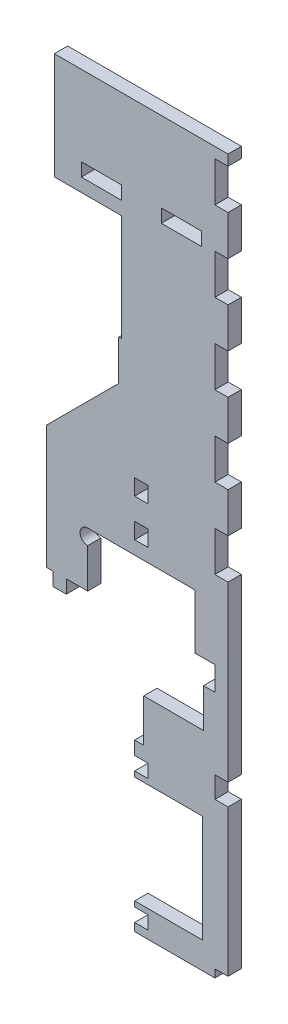
SolidWorks part; units mm, degrees
material "Balsa"
ref_plane "Plan de face" through (0, 0, 0) normal (0, 0, 1) x (1, 0, 0)
ref_plane "Plan de dessus" through (0, 0, 0) normal (0, 1, 0) x (1, 0, 0)
ref_plane "Plan de droite" through (0, 0, 0) normal (1, 0, 0) x (0, 0, -1)
sketch "Esquisse1" plane through (0, 0, 0) normal (0, 0, 1) x (1, 0, 0)
  line L0 (65.1211, 0) -> (30.1224, 0)
  line L2 (65.1211, 0) -> (65.1211, 270)
  line L3 (65.1211, 270) -> (0, 270)
  line L4 (0, 270) -> (0, 230)
  line L5 (0, 230) -> (24.1211, 230)
  line L6 (-2.8789, 101.7504) -> (12.493, 101.7504)
  line L7 (12.493, 101.7504) -> (12.493, 122.247)
  line L8 (12.493, 122.247) -> (52.693, 122.247)
  line L9 (52.693, 122.247) -> (52.693, 101.7504)
  line L10 (52.693, 101.7504) -> (55.9116, 101.7504)
  line L11 (1.3186, 101.7504) -> (30.1224, 101.7504) construction
  line L12 (55.9116, 101.7504) -> (55.9116, 78.2407)
  line L13 (55.9116, 78.2407) -> (33.5123, 78.2407)
  line L14 (33.5123, 78.2407) -> (33.5123, 62.2)
  line L15 (33.5123, 62.2) -> (30.1224, 62.2)
  line L16 (30.1224, 62.2) -> (30.1224, 57.2)
  line L17 (30.1224, 50.2) -> (55.6176, 50.2)
  line L18 (30.1224, 57.2) -> (35.1224, 57.2)
  line L19 (24.1211, 230) -> (24.1211, 175)
  line L20 (35.1224, 57.2) -> (35.1224, 52.2)
  line L21 (24.1211, 175) -> (-2.8789, 148)
  line L22 (-2.8789, 148) -> (-2.8789, 101.7504)
  line L23 (35.1224, 52.2) -> (30.1224, 52.2)
  line L24 (30.1224, 52.2) -> (30.1224, 50.2)
  line L25 (30.1224, 0) -> (30.1224, 3)
  line L26 (30.1224, 3) -> (35.1224, 3)
  line L27 (35.1224, 3) -> (35.1224, 8)
  line L30 (35.1224, 8) -> (30.1224, 8)
  line L31 (30.1224, 8) -> (30.1224, 10)
  line L32 (30.1224, 10) -> (55.6176, 10)
  line L33 (55.6176, 10) -> (55.6176, 50.2)
  dimension "D1" = 270
  dimension "D2" = 65.1211
  dimension "D3" = 40.2
  dimension "D4" = 2
  dimension "D5" = 20.4965
  dimension "D6" = 40.2
  dimension "D7" = 55
  dimension "D8" = 40
  dimension "D9" = 12.4281
  dimension "D10" = 25.4952
  dimension "D11" = 5
  dimension "D12" = 5
  dimension "D13" = 5
  dimension "D14" = 2
  dimension "D15" = 5
  dimension "D16" = 5
  dimension "D17" = 25.4952
  dimension "D18" = 135
  dimension "D19" = 41
  dimension "D20" = 68
extrude "Boss.-Extru.1" add sketch "Esquisse1" against normal blind 5
sketch "Esquisse2" plane through (0, 0, 0) normal (0, 0, 1) x (1, 0, 0)
  line L0 (52.693, 101.7504) -> (55.9116, 101.7504) construction
  line L1 (35.1224, 147.4016) -> (30.1224, 147.4016)
  line L2 (12.493, 122.247) -> (52.693, 122.247) construction
  line L3 (12.493, 101.7504) -> (12.493, 122.247) construction
  line L4 (35.1224, 147.4016) -> (35.1224, 141.4016)
  line L5 (35.1224, 141.4016) -> (30.1224, 141.4016)
  line L6 (30.1224, 147.4016) -> (30.1224, 141.4016)
  line L7 (35.1224, 133.247) -> (30.1224, 133.247)
  line L8 (35.1224, 133.247) -> (35.1224, 127.247)
  line L9 (35.1224, 127.247) -> (30.1224, 127.247)
  line L10 (30.1224, 133.247) -> (30.1224, 127.247)
  line L11 (55.9116, 101.7504) -> (60.186, 101.7504)
  line L12 (55.9116, 101.7504) -> (55.9116, 92.7704)
  line L13 (55.9116, 92.7704) -> (60.186, 92.7704)
  line L14 (60.186, 101.7504) -> (60.186, 92.7704)
  line L15 (52.693, 122.247) -> (52.693, 101.7504) construction
  line L16 (65.1211, 0) -> (65.1211, 270) construction
  line L17 (65.1211, 0) -> (60.2011, 0)
  line L18 (65.1211, 0) -> (65.1211, 3)
  line L19 (65.1211, 3) -> (60.2011, 3)
  line L20 (60.2011, 0) -> (60.2011, 3)
  line L21 (30.1224, 0) -> (65.1211, 0) construction
  line L22 (65.1211, 0) -> (65.1211, 270) construction
  line L23 (65.1211, 58) -> (60.2011, 58)
  line L24 (65.1211, 58) -> (65.1211, 66)
  line L25 (65.1211, 66) -> (60.2011, 66)
  line L26 (60.2011, 58) -> (60.2011, 66)
  line L27 (30.1224, 0) -> (65.1211, 0) construction
  line L28 (65.1211, 161) -> (60.2011, 161)
  line L29 (65.1211, 131) -> (60.2011, 131)
  line L30 (65.1211, 131) -> (65.1211, 146)
  line L31 (65.1211, 146) -> (60.2011, 146)
  line L32 (60.2011, 131) -> (60.2011, 146)
  line L33 (65.1211, 161) -> (65.1211, 176)
  line L34 (65.1211, 176) -> (60.2011, 176)
  line L35 (60.2011, 161) -> (60.2011, 176)
  line L36 (65.1211, 191) -> (60.2011, 191)
  line L37 (65.1211, 191) -> (65.1211, 206)
  line L38 (65.1211, 206) -> (60.2011, 206)
  line L39 (60.2011, 191) -> (60.2011, 206)
  line L40 (65.1211, 221) -> (60.2011, 221)
  line L41 (65.1211, 221) -> (65.1211, 236)
  line L42 (65.1211, 236) -> (60.2011, 236)
  line L43 (60.2011, 221) -> (60.2011, 236)
  line L44 (65.1211, 251) -> (60.2011, 251)
  line L45 (65.1211, 251) -> (65.1211, 266)
  line L46 (65.1211, 266) -> (60.2011, 266)
  line L47 (60.2011, 251) -> (60.2011, 266)
  line L49 (55.1211, 235) -> (40.1211, 235)
  line L50 (55.1211, 235) -> (55.1211, 240)
  line L51 (55.1211, 240) -> (40.1211, 240)
  line L52 (40.1211, 235) -> (40.1211, 240)
  line L53 (24.1211, 230) -> (24.1211, 175) construction
  line L54 (25.1211, 235) -> (10.1211, 235)
  line L55 (25.1211, 235) -> (25.1211, 240)
  line L56 (25.1211, 240) -> (10.1211, 240)
  line L57 (10.1211, 235) -> (10.1211, 240)
  line L58 (24.1211, 230) -> (25.1211, 230)
  line L59 (24.1211, 230) -> (24.1211, 190)
  line L60 (24.1211, 190) -> (25.1211, 190)
  line L61 (25.1211, 230) -> (25.1211, 190)
  line L62 (0, 230) -> (24.1211, 230) construction
  line L63 (65.1211, 270) -> (0, 270) construction
  circle A0 centre (12.493, 119.3895) radius 2.8575
  dimension "D1" = 2.8575
  dimension "D2" = 7.493
  dimension "D3" = 4.92
  dimension "D4" = 3
  dimension "D5" = 4.92
  dimension "D6" = 8
  dimension "D7" = 58
  dimension "D8" = 15
  dimension "D9" = 131
  dimension "D11" = 40
  dimension "D12" = 1
  dimension "D13" = 5
  dimension "D14" = 30
  dimension "D10" = 5
extrude "Enlèv. mat.-Extru.1" cut sketch "Esquisse2" against normal blind 5
sketch "Esquisse3" plane through (0, 0, 0) normal (0, 0, 1) x (1, 0, 0)
  line L1 (4.493, 101.7504) -> (-0.507, 101.7504)
  line L2 (4.493, 101.7504) -> (4.493, 96.7504)
  line L3 (4.493, 96.7504) -> (-0.507, 96.7504)
  line L4 (-0.507, 101.7504) -> (-0.507, 96.7504)
  line L6 (-2.8789, 101.7504) -> (12.493, 101.7504) construction
  line L7 (12.493, 101.7504) -> (12.493, 116.532) construction
  dimension "D1" = 8
  dimension "D2" = 5
  dimension "D3" = 5
extrude "Boss.-Extru.2" add sketch "Esquisse3" against normal blind 5
